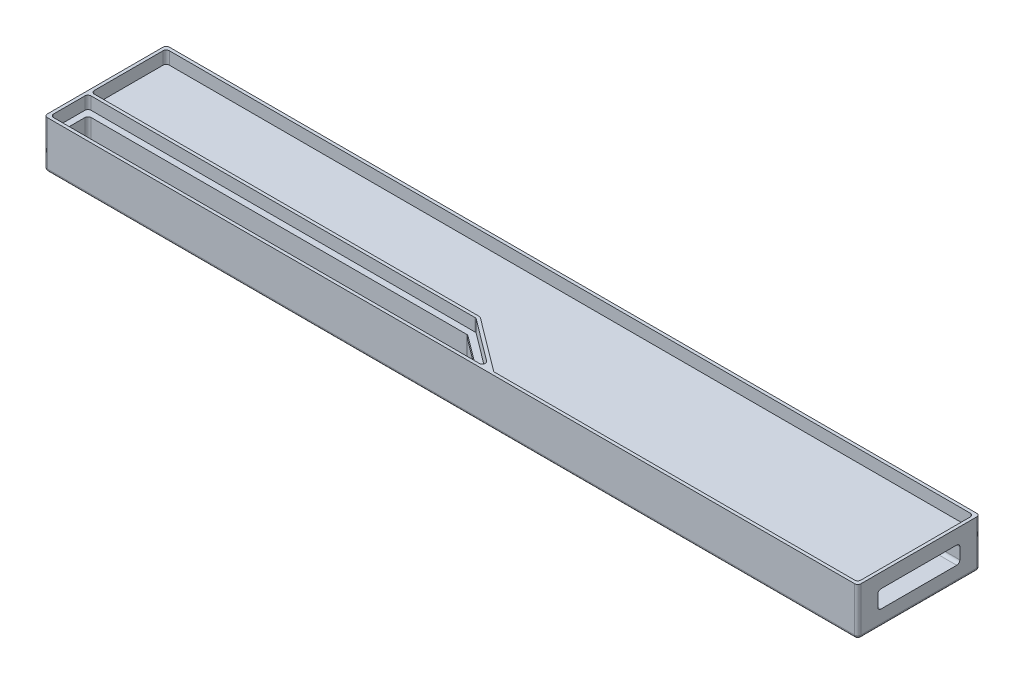
SolidWorks part; units mm, degrees
ref_plane "Спереди" through (0, 0, 0) normal (0, 0, 1) x (1, 0, 0)
ref_plane "Сверху" through (0, 0, 0) normal (0, 1, 0) x (1, 0, 0)
ref_plane "Справа" through (0, 0, 0) normal (1, 0, 0) x (0, 0, -1)
sketch "Эскиз1" plane through (0, 0, 0) normal (0, 1, 0) x (1, 0, 0)
  line L1 (-64.5, 9.75) -> (64.5, 9.75)
  line L2 (-65, 9.25) -> (-65, -9.25)
  line L3 (-64.5, -9.75) -> (64.5, -9.75)
  line L4 (65, 9.25) -> (65, -9.25)
  line L5 (-65, 9.75) -> (65, -9.75) construction
  line L6 (-65, -9.75) -> (65, 9.75) construction
  arc A0 (64.5, 9.75) -> (65, 9.25) centre (64.5, 9.25) cw
  arc A1 (64.5, -9.75) -> (65, -9.25) centre (64.5, -9.25) ccw
  arc A2 (-64.5, -9.75) -> (-65, -9.25) centre (-64.5, -9.25) cw
  arc A3 (-64.5, 9.75) -> (-65, 9.25) centre (-64.5, 9.25) ccw
  point P0 (0, 0)
  dimension "D3" = 0.5
  dimension "D1" = 130
  dimension "D2" = 19.5
extrude "Бобышка-Вытянуть1" add sketch "Эскиз1" along normal blind 7.6
sketch "Эскиз2" plane through (0, 7.6, 0) normal (0, 1, 0) x (1, 0, 0)
  line L1 (-64, -3.25) -> (-2.6667, -3.25)
  line L2 (-64.5, -3.75) -> (-64.5, -8.75)
  line L3 (5.5, -9.25) -> (-2.5, -3.25) construction
  line L4 (64.5, 9.75) -> (-64.5, 9.75) construction
  line L6 (-64.5, -3.25) -> (-2.5, -3.25) construction
  line L7 (4.3, -8.35) -> (-2.3667, -3.35)
  line L8 (-64, -9.25) -> (4, -9.25)
  line L9 (-64.5, -3.25) -> (-64.5, -9.25) construction
  line L10 (-64, 9.25) -> (64, 9.25)
  line L11 (64.5, -8.75) -> (64.5, 8.75)
  line L12 (-64.5, -2.25) -> (-64.5, 8.75)
  line L13 (-64, -2.75) -> (-2.5, -2.75)
  line L14 (6.2, -9.15) -> (-2.2, -2.85)
  line L15 (6.5, -9.25) -> (64, -9.25)
  line L16 (7, -9.75) -> (-2.3333, -2.75) construction
  line L17 (-65, -2.75) -> (-2.3333, -2.75) construction
  line L18 (-65, -2.75) -> (-65, -9.75) construction
  line L19 (-65, -9.75) -> (-2.5, -9.75) construction
  line L20 (-2.5, -9.75) -> (7, -9.75) construction
  line L21 (-64.5, -9.25) -> (-2.5, -9.25) construction
  line L22 (-2.5, -9.25) -> (5.5, -9.25) construction
  line L23 (65, -9.25) -> (65, 9.25) construction
  arc A0 (64.5, -8.75) -> (64, -9.25) centre (64, -8.75) cw
  arc A1 (64.5, 8.75) -> (64, 9.25) centre (64, 8.75) ccw
  arc A2 (-64, 9.25) -> (-64.5, 8.75) centre (-64, 8.75) ccw
  arc A3 (-64.5, -2.25) -> (-64, -2.75) centre (-64, -2.25) ccw
  arc A4 (6.5, -9.25) -> (6.2, -9.15) centre (6.5, -8.75) cw
  arc A5 (-2.5, -2.75) -> (-2.2, -2.85) centre (-2.5, -3.25) cw
  arc A6 (-2.3667, -3.35) -> (-2.6667, -3.25) centre (-2.6667, -3.75) ccw
  arc A7 (-64, -9.25) -> (-64.5, -8.75) centre (-64, -8.75) cw
  arc A8 (-64.5, -3.75) -> (-64, -3.25) centre (-64, -3.75) cw
  arc A9 (4, -9.25) -> (4.3, -8.35) centre (4, -8.75) ccw
  point P22 (64.5, -9.25)
  point P27 (-64.5, 9.25)
  point P32 (6.3333, -9.25)
  point P39 (-2.5, -3.25)
  dimension "D2" = 0.5
  dimension "D1" = 0.5
  dimension "D6" = 0.5
  dimension "D8" = 0.5
extrude "Вырез-Вытянуть1" cut sketch "Эскиз2" against normal blind 2
sketch "Эскиз6" plane through (0, 5.6, 0) normal (0, 1, 0) x (1, 0, 0)
  line L0 (-64.5, -9.75) -> (64.5, -9.75) construction
  line L1 (-64, -3.2382) -> (-2.6618, -3.2382)
  line L2 (-64.5, -3.7382) -> (-64.5, -8.75)
  line L3 (-63, -4.2382) -> (-2.9952, -4.2382)
  line L4 (-65, 9.25) -> (-65, -9.25) construction
  line L5 (1.3206, -7.35) -> (-2.6952, -4.3382)
  line L6 (-63, -8.25) -> (1.0206, -8.25)
  line L7 (4.3206, -8.35) -> (-2.3618, -3.3382)
  line L8 (-64, -9.25) -> (4.0206, -9.25)
  line L9 (-63.5, -4.7382) -> (-63.5, -7.75)
  line L10 (-63.5, -8.25) -> (2.5206, -8.25) construction
  line L11 (2.5206, -8.25) -> (-2.8285, -4.2382) construction
  line L12 (-63.5, -4.2382) -> (-2.8285, -4.2382) construction
  line L13 (-63.5, -4.2382) -> (-63.5, -8.25) construction
  arc A0 (-63, -8.25) -> (-63.5, -7.75) centre (-63, -7.75) cw
  arc A1 (-2.6952, -4.3382) -> (-2.9952, -4.2382) centre (-2.9952, -4.7382) ccw
  arc A2 (-63.5, -4.7382) -> (-63, -4.2382) centre (-63, -4.7382) cw
  arc A4 (1.0206, -8.25) -> (1.3206, -7.35) centre (1.0206, -7.75) ccw
  arc A6 (-2.3618, -3.3382) -> (-2.6618, -3.2382) centre (-2.6618, -3.7382) ccw
  arc A7 (-64, -9.25) -> (-64.5, -8.75) centre (-64, -8.75) cw
  arc A8 (-64.5, -3.7382) -> (-64, -3.2382) centre (-64, -3.7382) cw
  arc A9 (4.0206, -9.25) -> (4.3206, -8.35) centre (4.0206, -8.75) ccw
  arc A10 (2.5206, -8.25) -> (2.5206, -8.25) centre (2.5206, -8.25) ccw construction
  arc A11 (-2.8285, -4.2382) -> (-2.8285, -4.2382) centre (-2.8285, -4.2382) ccw construction
  arc A12 (-63.5, -8.25) -> (-63.5, -8.25) centre (-63.5, -8.25) cw construction
  arc A13 (-63.5, -4.2382) -> (-63.5, -4.2382) centre (-63.5, -4.2382) cw construction
  point P4 (0, 0)
  point P39 (-2.4952, -3.2382)
  dimension "D2" = 1
  dimension "D4" = 0.5
  dimension "D1" = 0.5
  dimension "D3" = 0.5
extrude "Вырез-Вытянуть2" cut sketch "Эскиз6" against normal through all contours L6 A4 L5 A1 L3 A2 L9 A0 region at (-31.8531, 5.6, 6.2694)
sketch "Эскиз7" plane through (0, 0, 0) normal (0, -1, 0) x (1, 0, 0)
  line L0 (-64.5, 9.75) -> (64.5, 9.75) construction
  line L1 (-63, 4.25) -> (59.5, 4.25)
  line L2 (-63.5, 4.75) -> (-63.5, 7.75)
  line L3 (-63, 8.25) -> (59.5, 8.25)
  line L4 (60, 4.75) -> (60, 7.75)
  line L5 (-65, -9.25) -> (-65, 9.25) construction
  line L6 (64.5, -9.75) -> (-64.5, -9.75) construction
  line L7 (59.5, -7.75) -> (41, -7.75)
  line L8 (60, -7.25) -> (60, 1.75)
  line L9 (59.5, 2.25) -> (41, 2.25)
  line L10 (40.5, -7.25) -> (40.5, 1.75)
  line L11 (65, 9.25) -> (65, -9.25) construction
  line L13 (-61.74, -8.15) -> (-61.76, -8.15)
  line L14 (-60, -6.41) -> (-60, 1.11)
  line L15 (-61.74, 2.85) -> (-61.76, 2.85)
  line L16 (-63.5, -6.41) -> (-63.5, 1.11)
  arc A0 (-63.5, 7.75) -> (-63, 8.25) centre (-63, 7.75) cw
  arc A1 (-63.5, 4.75) -> (-63, 4.25) centre (-63, 4.75) ccw
  arc A2 (60, 7.75) -> (59.5, 8.25) centre (59.5, 7.75) ccw
  arc A3 (59.5, 4.25) -> (60, 4.75) centre (59.5, 4.75) ccw
  arc A4 (60, 1.75) -> (59.5, 2.25) centre (59.5, 1.75) ccw
  arc A5 (41, 2.25) -> (40.5, 1.75) centre (41, 1.75) ccw
  arc A6 (40.5, -7.25) -> (41, -7.75) centre (41, -7.25) ccw
  arc A7 (59.5, -7.75) -> (60, -7.25) centre (59.5, -7.25) ccw
  arc A8 (-60, 1.11) -> (-61.74, 2.85) centre (-61.74, 1.11) ccw
  arc A9 (-61.76, 2.85) -> (-63.5, 1.11) centre (-61.76, 1.11) ccw
  arc A10 (-63.5, -6.41) -> (-61.76, -8.15) centre (-61.76, -6.41) ccw
  arc A11 (-61.74, -8.15) -> (-60, -6.41) centre (-61.74, -6.41) ccw
  point P10 (-63.5, 8.25)
  point P13 (-63.5, 4.25)
  point P16 (60, 8.25)
  point P29 (60, 2.25)
  point P34 (40.5, -7.75)
  point P37 (60, -7.75)
  point P44 (-60, 2.85)
  point P49 (-63.5, -8.15)
  point P52 (-60, -8.15)
  dimension "D5" = 0.5
  dimension "D10" = 0.5
  dimension "D15" = 1.74
  dimension "D1" = 4
  dimension "D2" = 1.5
  dimension "D3" = 1.5
  dimension "D4" = 123.5
  dimension "D6" = 19.5
  dimension "D7" = 10
  dimension "D8" = 2
  dimension "D9" = 5
  dimension "D11" = 3.5
  dimension "D12" = 11
  dimension "D13" = 1.6
  dimension "D14" = 1.5
extrude "Вырез-Вытянуть3" cut sketch "Эскиз7" against normal blind 1.6
sketch "Эскиз8" plane through (0, 1.6, 0) normal (0, -1, 0) x (1, 0, 0)
  line L0 (-64.5, 9.75) -> (64.5, 9.75) construction
  line L1 (-63, 8.25) -> (40, 8.25)
  line L2 (-63.5, 7.75) -> (-63.5, 4.75)
  line L3 (-63, 4.25) -> (40, 4.25)
  line L4 (40.5, 7.75) -> (40.5, 4.75)
  line L5 (-65, -9.25) -> (-65, 9.25) construction
  arc A0 (-63, 4.25) -> (-63.5, 4.75) centre (-63, 4.75) cw
  arc A1 (-63.5, 7.75) -> (-63, 8.25) centre (-63, 7.75) cw
  arc A2 (40, 8.25) -> (40.5, 7.75) centre (40, 7.75) cw
  arc A3 (40, 4.25) -> (40.5, 4.75) centre (40, 4.75) ccw
  point P10 (-63.5, 4.25)
  point P13 (-63.5, 8.25)
  point P16 (40.5, 8.25)
  dimension "D5" = 0.5
  dimension "D1" = 4
  dimension "D2" = 1.5
  dimension "D3" = 1.5
  dimension "D4" = 104
extrude "Вырез-Вытянуть4" cut sketch "Эскиз8" against normal blind 3.3
sketch "Эскиз9" plane through (65, 0, 0) normal (1, 0, 0) x (0, 0, -1)
  line L0 (-9.75, 7.6) -> (-9.75, 0) construction
  line L1 (-6.05, 5.3) -> (6.05, 5.3)
  line L2 (-6.55, 4.8) -> (-6.55, 3)
  line L3 (-6.05, 2.5) -> (6.05, 2.5)
  line L4 (6.55, 4.8) -> (6.55, 3)
  line L5 (-9.25, 7.6) -> (9.25, 7.6) construction
  arc A0 (6.05, 5.3) -> (6.55, 4.8) centre (6.05, 4.8) cw
  arc A1 (6.55, 3) -> (6.05, 2.5) centre (6.05, 3) cw
  arc A2 (-6.05, 2.5) -> (-6.55, 3) centre (-6.05, 3) cw
  arc A3 (-6.05, 5.3) -> (-6.55, 4.8) centre (-6.05, 4.8) ccw
  point P10 (6.55, 5.3)
  point P15 (-6.55, 2.5)
  point P18 (-6.55, 5.3)
  dimension "D5" = 0.5
  dimension "D1" = 3.2
  dimension "D2" = 2.3
  dimension "D3" = 13.1
  dimension "D4" = 2.8
extrude "Вырез-Вытянуть5" cut sketch "Эскиз9" against normal blind 10
fillet "Скругление1" radius 0.5 8 edges at (64.8536, 0, 9.6036) (64.8536, 0, -9.6036) (-64.8536, 0, 9.6036) (-64.8536, 0, -9.6036) (-65, 0, 0) (0, 0, 9.75) (65, 0, 0) (0, 0, -9.75)
